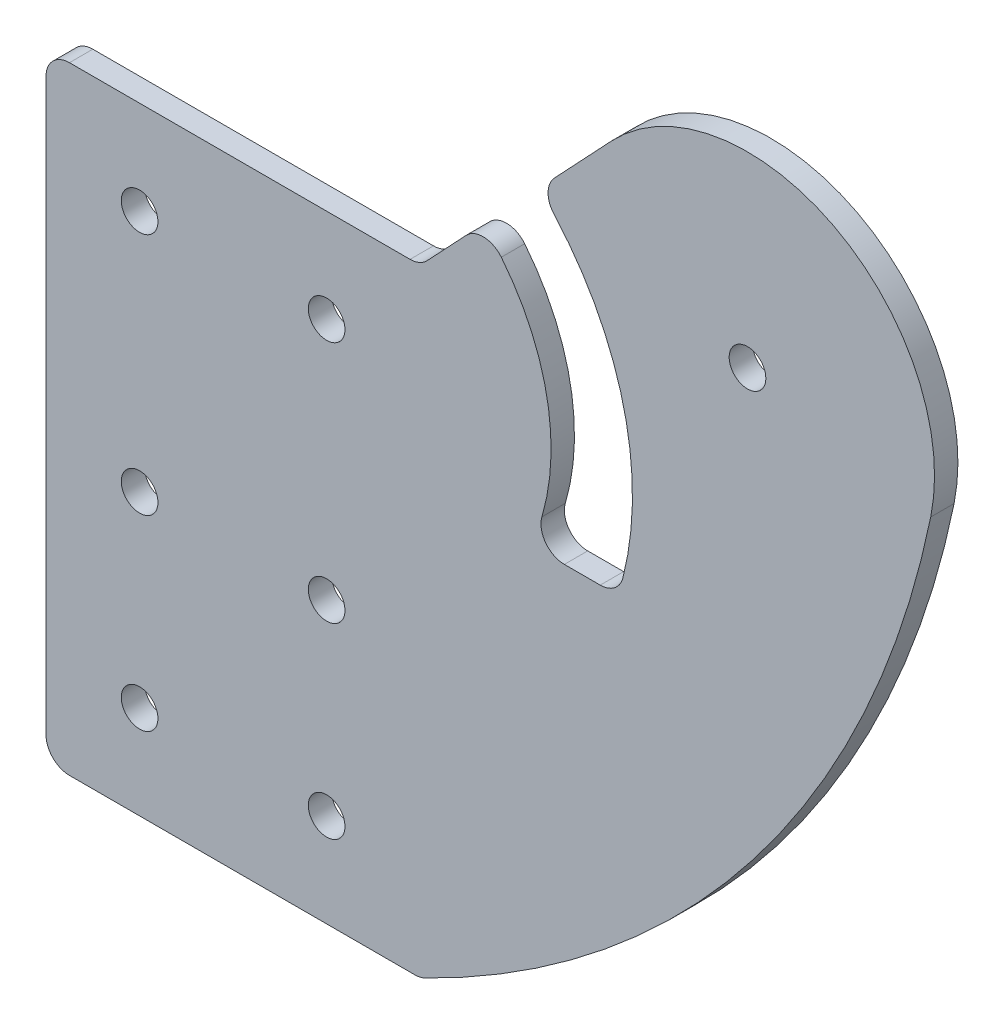
SolidWorks part; units mm, degrees
material "6061-T6 (SS)"
ref_plane "Front Plane" through (0, 0, 0) normal (0, 0, 1) x (1, 0, 0)
ref_plane "Top Plane" through (0, 0, 0) normal (0, 1, 0) x (1, 0, 0)
ref_plane "Right Plane" through (0, 0, 0) normal (1, 0, 0) x (0, 0, -1)
sketch "Sketch2" plane through (0, 0, 0) normal (0, 0, 1) x (1, 0, 0)
  line L0 (50.8, 83.82) -> (59.1187, 92.6561)
  line L1 (0, 0) -> (50.8, 0)
  line L2 (0, 0) -> (0, 83.82)
  line L3 (0, 83.82) -> (50.8, 83.82)
  line L11 (59.1187, 92.6561) -> (59.384, 92.938)
  line L12 (65.8081, 58.42) -> (77.6394, 58.42)
  line L14 (76.7561, 111.3908) -> (66.9585, 100.9837)
  circle A2 centre (95.25, 93.98) radius 2.4892
  arc A3 (50.8, 0) -> (120.1297, 88.8651) centre (-4.2686, 114.4397) ccw
  circle A4 centre (38.1, 71.12) radius 2.4892 construction
  circle A5 centre (13.208, 97.028) radius 4.7625 construction
  arc A8 (120.1297, 88.8651) -> (76.7561, 111.3908) centre (95.25, 93.98) ccw
  arc A9 (65.8081, 58.42) -> (59.384, 92.938) centre (38.1, 71.12) ccw
  arc A10 (77.6394, 58.42) -> (66.9585, 100.9837) centre (38.1, 71.12) ccw
  dimension "D3" = 50.8
  dimension "D5" = 95.25
  dimension "D4" = 4.9784
  dimension "D7" = 254
  dimension "D11" = 4.9784
  dimension "D8" = 60.96
  dimension "D9" = 83.058
  dimension "D16" = 9.525
  dimension "D1" = 50.8
  dimension "D2" = 83.82
  dimension "D6" = 93.98
  dimension "D10" = 25.4
  dimension "D12" = 38.1
  dimension "D13" = 12.7
  dimension "D14" = 25.908
  dimension "D15" = 24.892
extrude "Boss-Extrude1" add sketch "Sketch2" against normal blind 3.175
sketch "Sketch3" plane through (0, 0, 0) normal (0, 0, 1) x (1, 0, 0)
  line L0 (50.8, 83.82) -> (0, 83.82) construction
  line L1 (0, 83.82) -> (0, 0) construction
  circle A0 centre (12.7, 71.12) radius 2.4892
  circle A17 centre (38.1, 71.12) radius 2.4892
  circle A24 centre (12.7, 38.1) radius 2.4892
  circle A25 centre (12.7, 12.7) radius 2.4892
  circle A26 centre (12.7, -12.7) radius 2.4892
  circle A27 centre (12.7, -38.1) radius 2.4892
  circle A28 centre (12.7, -63.5) radius 2.4892
  circle A33 centre (38.1, 12.7) radius 2.4892
  circle A34 centre (38.1, -12.7) radius 2.4892
  circle A35 centre (38.1, -38.1) radius 2.4892
  circle A36 centre (38.1, -63.5) radius 2.4892
  circle A41 centre (38.1, 38.1) radius 2.4892
  dimension "D1" = 4.9784
  dimension "D6" = 4.9784
  dimension "D2" = 12.7
  dimension "D3" = 12.7
  dimension "D7" = 12.7
  dimension "D8" = 33.02
  dimension "D4" = 1
  dimension "D5" = 2
  dimension "D9" = 5
  dimension "D10" = 2
extrude "Cut-Extrude1" cut sketch "Sketch3" against normal through all
fillet "Fillet1" radius 3.175 8 edges at (0, 0, -1.5875) (50.8, 83.82, -1.5875) (0, 83.82, -1.5875) (50.8, 0, -1.5875) (77.6394, 58.42, -1.5875) (65.8081, 58.42, -1.5875) (59.384, 92.938, -1.5875) (66.9585, 100.9837, -1.5875)
